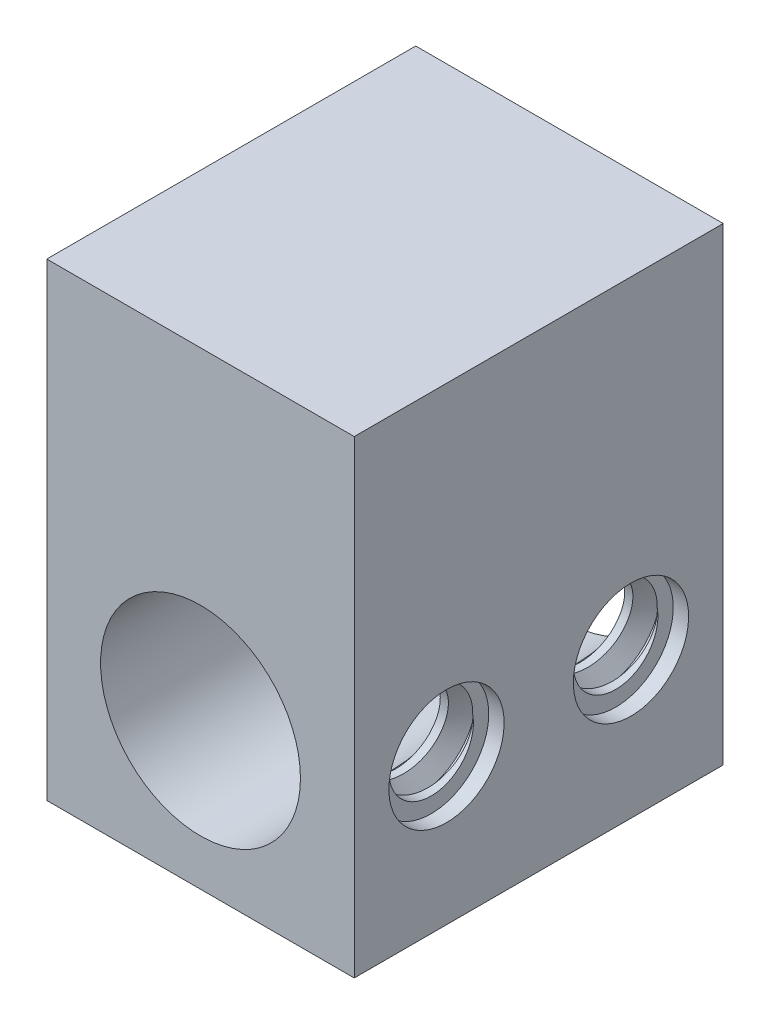
SolidWorks part; units mm, degrees
ref_plane "Front Plane" through (0, 0, 0) normal (0, 0, 1) x (1, 0, 0)
ref_plane "Top Plane" through (0, 0, 0) normal (0, 1, 0) x (1, 0, 0)
ref_plane "Right Plane" through (0, 0, 0) normal (1, 0, 0) x (0, 0, -1)
sketch "Sketch1" plane through (0, 0, 0) normal (0, 0, 1) x (1, 0, 0)
  line L1 (0, 0) -> (-20, 0)
  line L2 (0, 0) -> (0, -30.5)
  line L3 (0, -30.5) -> (-20, -30.5)
  line L4 (-20, 0) -> (-20, -30.5)
  dimension "D1" = 20
  dimension "D2" = 30.5
extrude "Boss-Extrude1" add sketch "Sketch1" along normal blind 24
sketch "Sketch2" plane through (0, 0, 24) normal (0, 0, 1) x (1, 0, 0)
  line L1 (0, 0) -> (-20, 0) construction
  line L2 (-20, -30.5) -> (0, -30.5) construction
  circle A0 centre (-10, -21) radius 6.5
  point P7 (-10, 0)
  dimension "D1" = 9.5
  dimension "D2" = 0
  dimension "D3" = 13
extrude "Cut-Extrude1" cut sketch "Sketch2" against normal blind 40
sketch "Sketch8" plane through (0, 0, 0) normal (0, 0, -1) x (-1, 0, 0)
  line L0 (0, 0) -> (20, 0) construction
  circle A0 centre (10, -10.5) radius 2
  point P4 (10, 0)
  dimension "D1" = 0
  dimension "D2" = 4
  dimension "D3" = 10.5
extrude "Cut-Extrude5" cut sketch "Sketch8" against normal blind 20
sketch "Sketch13" plane through (0, 0, 0) normal (1, 0, 0) x (0, 0, -1)
  line L0 (-24, -30.5) -> (0, -30.5) construction
  line L1 (0, -30.5) -> (0, 0) construction
  circle A0 centre (-6, -21) radius 2.75
  dimension "D1" = 9.5
  dimension "D2" = 5.5
  dimension "D3" = 6
extrude "Cut-Extrude8" cut sketch "Sketch13" against normal blind 10
thread "Thread3" pitch 2.1167 method cut profile "Thread Profile3" start angle 0, offset 0, length 10, pitch 2.1167, diameter 5.5
ref_plane "Plane3" through (0, -21, 8.75) normal (0, -1, 0) x (0, 0, 1)
sketch "Thread Profile3" plane through (0, -21, 8.75) normal (0, -1, 0) x (0, 0, 1)
  line L0 (0, 0) -> (0, 2.1167) construction
  line L1 (0, 0) -> (1.1457, 0.6615)
  line L2 (1.1457, 0.6615) -> (1.1457, 0.926)
  line L3 (1.1457, 0.926) -> (0, 1.5875)
  line L4 (1.1457, 0.7937) -> (0, 0.7937) construction
  line L11 (0, 0) -> (0, 1.5875)
  point P2 (0, 0)
  dimension "Pitch" = 2.1167
  dimension "Profile_Angle" = 60
  dimension "Profile_Land" = 0.2646
  dimension "Profile_Height" = 1.1457
sketch "Sketch16" plane through (0, 0, 0) normal (1, 0, 0) x (0, 0, -1)
  circle A0 centre (-6, -21) radius 3.75
  dimension "D1" = 7.5
extrude "Cut-Extrude9" cut sketch "Sketch16" against normal blind 1
sketch "Sketch19" plane through (0, 0, 0) normal (1, 0, 0) x (0, 0, -1)
  line L0 (-24, -30.5) -> (-24, 0) construction
  circle A0 centre (-18, -21) radius 2.75
  circle A2 centre (-6, -21) radius 3.75 construction
  dimension "D1" = 6
  dimension "D2" = 5.5
  dimension "D3" = 0
extrude "Cut-Extrude11" cut sketch "Sketch19" against normal blind 10
thread "Thread4" pitch 2.1167 method cut profile "Thread Profile4" start angle 0, offset 0, length 10, pitch 2.1167, diameter 5.5
ref_plane "Plane4" through (0, -21, 20.75) normal (0, -1, 0) x (0, 0, 1)
sketch "Thread Profile4" plane through (0, -21, 20.75) normal (0, -1, 0) x (0, 0, 1)
  line L0 (0, 0) -> (0, 2.1167) construction
  line L1 (0, 0) -> (1.1457, 0.6615)
  line L2 (1.1457, 0.6615) -> (1.1457, 0.926)
  line L3 (1.1457, 0.926) -> (0, 1.5875)
  line L4 (1.1457, 0.7937) -> (0, 0.7937) construction
  line L11 (0, 0) -> (0, 1.5875)
  point P2 (0, 0)
  dimension "Pitch" = 2.1167
  dimension "Profile_Angle" = 60
  dimension "Profile_Land" = 0.2646
  dimension "Profile_Height" = 1.1457
sketch "Sketch22" plane through (0, 0, 0) normal (1, 0, 0) x (0, 0, -1)
  circle A0 centre (-18, -21) radius 3.75
  dimension "D1" = 7.5
extrude "Cut-Extrude12" cut sketch "Sketch22" against normal blind 1
sketch "Sketch23" plane through (0, 0, 0) normal (0, 0, -1) x (-1, 0, 0)
  line L0 (0, -30.5) -> (0, 0) construction
  line L1 (5, -4) -> (2, -4)
  line L2 (5, -4) -> (5, -10)
  line L3 (5, -10) -> (2, -10)
  line L4 (2, -4) -> (2, -10)
  line L5 (0, 0) -> (20, 0) construction
  dimension "D1" = 2
  dimension "D2" = 3
  dimension "D3" = 6
  dimension "D4" = 4
extrude "Cut-Extrude13" cut sketch "Sketch23" against normal blind 14
